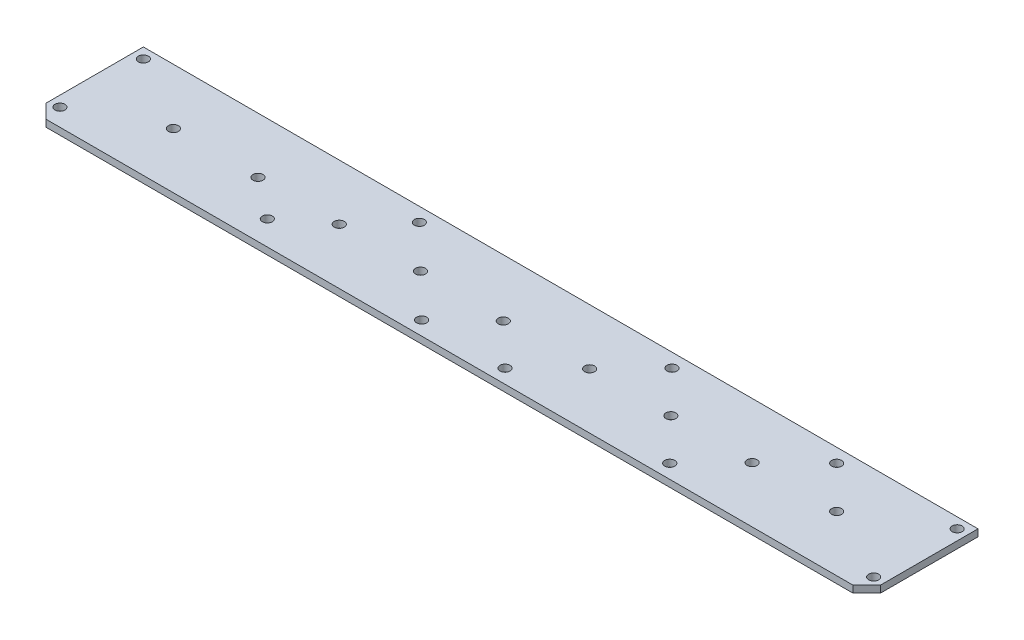
SolidWorks part; units mm, degrees
ref_plane "Front Plane" through (0, 0, 0) normal (0, 0, 1) x (1, 0, 0)
ref_plane "Top Plane" through (0, 0, 0) normal (0, 1, 0) x (1, 0, 0)
ref_plane "Right Plane" through (0, 0, 0) normal (1, 0, 0) x (0, 0, -1)
sketch "Sketch2" plane through (0, 0, 0) normal (0, 1, 0) x (1, 0, 0)
  line L0 (0, 0) -> (0, 50.8)
  line L1 (0, 50.8) -> (381, 50.8)
  line L2 (381, 50.8) -> (381, 0)
  line L3 (381, 0) -> (0, 0)
  dimension "D1" = 50.8
  dimension "D2" = 381
extrude "Boss-Extrude1" add sketch "Sketch2" along normal blind 3.175
sketch "Sketch3" plane through (0, 0, 0) normal (0, 1, 0) x (1, 0, 0)
  line L0 (0, 6.35) -> (6.35, 0) construction
  line L1 (374.65, 0) -> (381, 6.35) construction
  line L2 (0, 6.35) -> (6.35, 0)
  line L3 (374.65, 0) -> (381, 6.35)
  line L4 (0, 6.35) -> (0, 0)
  line L5 (0, 0) -> (6.35, 0)
  line L7 (381, 6.35) -> (381, 0)
  line L8 (381, 0) -> (374.65, 0)
  circle A19 centre (96.266, 11.1125) radius 2.286 construction
  circle A20 centre (284.734, 6.35) radius 2.286 construction
  circle A21 centre (322.834, 44.45) radius 2.286 construction
  circle A22 centre (132.334, 44.45) radius 2.286 construction
  circle A23 centre (247.65, 44.45) radius 2.286 construction
  circle A24 centre (209.55, 6.35) radius 2.286 construction
  circle A25 centre (171.45, 6.35) radius 2.286 construction
  circle A26 centre (4.7625, 7.9375) radius 2.286 construction
  circle A27 centre (4.7625, 46.0375) radius 2.286 construction
  circle A28 centre (39.116, 25.4) radius 2.286 construction
  circle A29 centre (77.724, 25.4) radius 2.286 construction
  circle A30 centre (114.808, 25.4) radius 2.286 construction
  circle A32 centre (190.5, 24.6062) radius 2.286 construction
  circle A36 centre (341.884, 25.4) radius 2.286 construction
  circle A37 centre (376.2375, 7.9375) radius 2.286 construction
  circle A38 centre (376.2375, 46.0375) radius 2.286 construction
  circle A39 centre (96.266, 11.1125) radius 2.286
  circle A40 centre (284.734, 6.35) radius 2.286
  circle A41 centre (322.834, 44.45) radius 2.286
  circle A42 centre (132.334, 44.45) radius 2.286
  circle A43 centre (247.65, 44.45) radius 2.286
  circle A44 centre (209.55, 6.35) radius 2.286
  circle A45 centre (171.45, 6.35) radius 2.286
  circle A46 centre (4.7625, 7.9375) radius 2.286
  circle A47 centre (4.7625, 46.0375) radius 2.286
  circle A48 centre (39.116, 25.4) radius 2.286
  circle A49 centre (77.724, 25.4) radius 2.286
  circle A50 centre (114.808, 25.4) radius 2.286
  circle A52 centre (190.5, 24.6062) radius 2.286
  circle A56 centre (341.884, 25.4) radius 2.286
  circle A57 centre (376.2375, 7.9375) radius 2.286
  circle A58 centre (376.2375, 46.0375) radius 2.286
  circle A59 centre (303.276, 25.4) radius 2.286
  circle A60 centre (266.192, 25.4) radius 2.286
  circle A61 centre (229.108, 25.4) radius 2.286
  circle A62 centre (151.892, 25.4) radius 2.286
  dimension "D1" = 4.572
extrude "Cut-Extrude1" cut sketch "Sketch3" along normal through all
